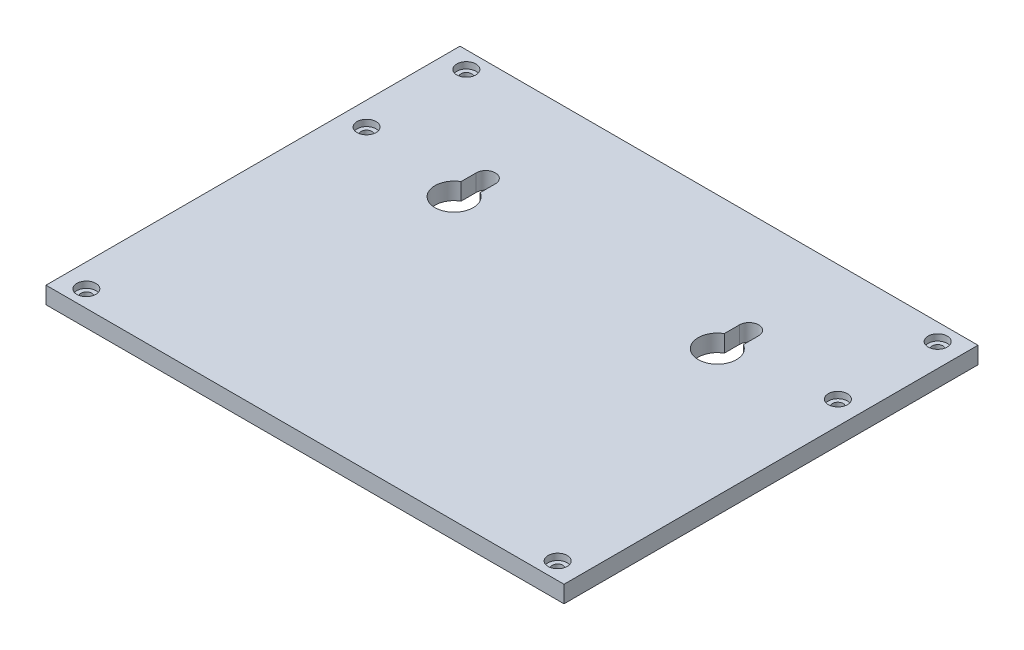
SolidWorks part; units mm, degrees
ref_plane "Front Plane" through (0, 0, 0) normal (0, 0, 1) x (1, 0, 0)
ref_plane "Top Plane" through (0, 0, 0) normal (0, 1, 0) x (1, 0, 0)
ref_plane "Right Plane" through (0, 0, 0) normal (1, 0, 0) x (0, 0, -1)
sketch "Sketch1" plane through (0, 0, 0) normal (0, 1, 0) x (1, 0, 0)
  line L1 (-91.4063, 40.0781) -> (30.5937, 40.0781)
  line L2 (-91.4063, 40.0781) -> (-91.4063, -57.4219)
  line L3 (-91.4063, -57.4219) -> (30.5938, -57.4219)
  line L4 (30.5937, 40.0781) -> (30.5938, -57.4219)
  dimension "D1" = 97.5
  dimension "D2" = 122
extrude "Boss-Extrude1" add sketch "Sketch1" along normal blind 4
sketch "Sketch2" plane through (0, 4, 0) normal (0, 1, 0) x (1, 0, 0)
  line L0 (-91.4063, 40.0781) -> (-91.4063, -57.4219) construction
  line L1 (30.5937, 40.0781) -> (-91.4063, 40.0781) construction
  line L2 (-91.4063, -57.4219) -> (30.5938, -57.4219) construction
  line L3 (30.5938, -57.4219) -> (30.5937, 40.0781) construction
  circle A0 centre (-85.9063, -53.4219) radius 1.25
  circle A1 centre (-85.9063, 12.5781) radius 1.25
  circle A2 centre (25.0938, 12.5781) radius 1.25
  circle A3 centre (25.0937, -53.4219) radius 1.25
  circle A4 centre (-85.9063, 36.0781) radius 1.25
  circle A5 centre (25.0938, 36.0781) radius 1.25
  point P18 (25.0938, 34.4206)
  point P19 (-85.9063, 34.4206)
  dimension "D1" = 4
  dimension "D2" = 5.5
  dimension "D3" = 5.5
  dimension "D4" = 66
  dimension "D5" = 5.5
  dimension "D6" = 5.5
  dimension "D7" = 66
  dimension "D8" = 4
  dimension "D9" = 4
  dimension "D10" = 4
extrude "Cut-Extrude1" cut sketch "Sketch2" against normal blind 4
sketch "Sketch3" plane through (0, 4, 0) normal (0, 1, 0) x (1, 0, 0)
  circle A0 centre (-85.9063, 12.5781) radius 2.25
  circle A1 centre (-85.9063, -53.4219) radius 2.25
  circle A2 centre (25.0937, -53.4219) radius 2.25
  circle A3 centre (25.0938, 12.5781) radius 2.25
  circle A5 centre (-85.9063, 36.0781) radius 2.25
  circle A6 centre (25.0938, 36.0781) radius 2.25
  point P14 (-85.9063, 36.0781)
  point P18 (25.0938, 35.2626)
  point P19 (25.0938, 36.0781)
  point P20 (0, 0)
  dimension "D1" = 4.5
  dimension "D2" = 4.5
  dimension "D3" = 4.5
  dimension "D4" = 4.5
extrude "Cut-Extrude2" cut sketch "Sketch3" against normal blind 1.5
sketch "Sketch4" plane through (0, 4, 0) normal (0, 1, 0) x (1, 0, 0)
  line L3 (-1.6563, 16.1573) -> (-1.6563, 12.5863)
  line L4 (-63.6563, 16.1573) -> (-63.6563, 12.5863)
  line L6 (-59.1563, 16.1573) -> (-59.1563, 12.5863)
  line L7 (2.8437, 16.1573) -> (2.8437, 12.5863)
  arc A2 (-59.1563, 12.5863) -> (-63.6563, 12.5863) centre (-61.4063, 8.6896) cw
  arc A4 (-63.6563, 16.1573) -> (-59.1563, 16.1573) centre (-61.4063, 16.1573) cw
  arc A7 (-1.6563, 16.1573) -> (2.8437, 16.1573) centre (0.5937, 16.1573) cw
  arc A8 (2.8437, 12.5863) -> (-1.6563, 12.5863) centre (0.5937, 8.6896) cw
  dimension "D1" = 2
  dimension "D3" = 4.5
extrude "Cut-Extrude3" cut sketch "Sketch4" against normal blind 4
